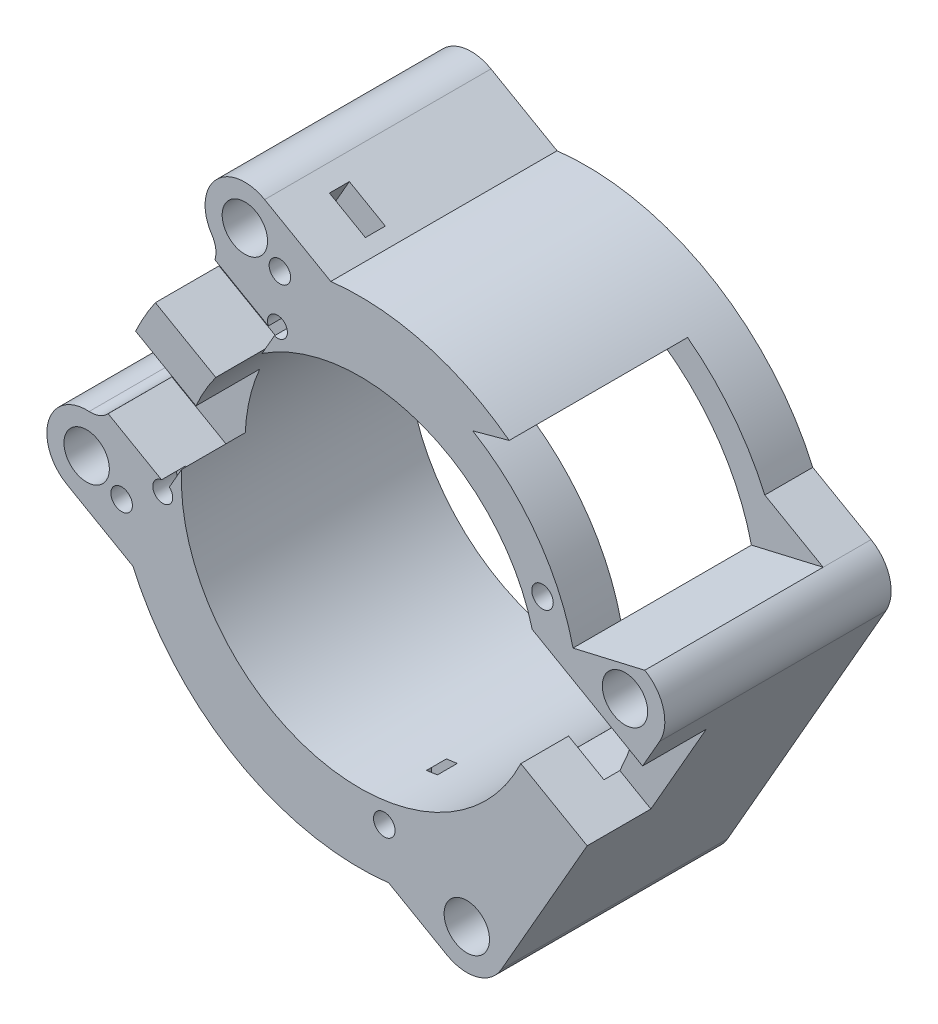
SolidWorks part; units mm, degrees
ref_plane "Front Plane" through (0, 0, 0) normal (0, 0, 1) x (1, 0, 0)
ref_plane "Top Plane" through (0, 0, 0) normal (0, 1, 0) x (1, 0, 0)
ref_plane "Right Plane" through (0, 0, 0) normal (1, 0, 0) x (0, 0, -1)
sketch "Sketch1" plane through (0, 0, 0) normal (0, 0, 1) x (1, 0, 0)
  line L0 (343.92, -196.825) -> (323.9579, -185.4007) construction
  line L1 (323.9579, -185.4007) -> (333.8921, -168.0424) construction
  line L2 (343.92, -196.825) -> (356.9388, -204.2756) construction
  line L3 (356.9388, -204.2756) -> (366.8729, -186.9173) construction
  line L4 (381.5729, -195.33) -> (361.7045, -230.0467) construction
  line L5 (350.2637, -176.9635) -> (357.8812, -174.8913) construction
  line L6 (367.0681, -208.6641) -> (359.4506, -210.7362) construction
  line L7 (350.2637, -176.9635) -> (357.8812, -174.8913) construction
  line L8 (367.0681, -208.6641) -> (359.4506, -210.7362) construction
  line L9 (350.381, -175.377) -> (358.1166, -173.2728)
  line L10 (368.091, -209.9404) -> (360.3554, -212.0446)
  line L11 (368.091, -209.9404) -> (359.8443, -212.1836) construction
  line L12 (349.8699, -175.5161) -> (358.1166, -173.2728) construction
  line L13 (315.4468, -209.3344) -> (21.5627, -41.1449) construction
  line L14 (354.8814, -231.9028) -> (347.5578, -227.7115) construction
  line L15 (372.3932, -184.3156) -> (379.7168, -188.5069) construction
  line L16 (32.0065, 10.4873) -> (340.2822, -165.9385) construction
  line L17 (315.4468, -209.3344) -> (307.1459, -204.5838)
  line L18 (354.8814, -231.9028) -> (347.5578, -227.7115)
  line L19 (381.5729, -195.33) -> (361.7045, -230.0467)
  line L20 (372.3932, -184.3156) -> (379.7168, -188.5069)
  line L21 (331.9813, -161.1879) -> (340.2822, -165.9385)
  circle A0 centre (329.4978, -165.5275) radius 1.65 construction
  circle A1 centre (309.6295, -200.2442) radius 1.65 construction
  circle A2 centre (357.3649, -227.5632) radius 1.65 construction
  circle A3 centre (377.2333, -192.8465) radius 1.65 construction
  circle A4 centre (329.4978, -165.5275) radius 1.65
  circle A5 centre (309.6295, -200.2442) radius 1.65
  circle A6 centre (357.3649, -227.5632) radius 1.65
  circle A7 centre (377.2333, -192.8465) radius 1.65
  circle A8 centre (333.8921, -168.0424) radius 1.35
  circle A9 centre (366.8729, -186.9173) radius 1.35
  circle A10 centre (347.0046, -221.634) radius 1.35
  circle A11 centre (314.0237, -202.7591) radius 1.35
  circle A12 centre (343.92, -196.825) radius 20.9 construction
  arc A13 (323.7528, -202.3109) -> (364.0872, -191.3391) centre (343.92, -196.825) ccw construction
  arc A14 (367.0681, -208.6641) -> (357.8812, -174.8913) centre (343.92, -196.825) ccw construction
  arc A15 (367.0681, -208.6641) -> (357.8812, -174.8913) centre (343.92, -196.825) ccw construction
  arc A16 (368.091, -209.9404) -> (358.1166, -173.2728) centre (343.92, -196.825) ccw
  arc A17 (350.381, -175.377) -> (360.3554, -212.0446) centre (343.92, -196.825) ccw
  circle A18 centre (343.92, -196.825) radius 22.4 construction
  arc A19 (315.4468, -209.3344) -> (347.5578, -227.7115) centre (343.92, -196.825) ccw construction
  arc A20 (354.8814, -231.9028) -> (361.7045, -230.0467) centre (357.3649, -227.5632) ccw construction
  arc A21 (381.5729, -195.33) -> (379.7168, -188.5069) centre (377.2333, -192.8465) ccw construction
  arc A22 (372.3932, -184.3156) -> (340.2822, -165.9385) centre (343.92, -196.825) ccw construction
  arc A23 (315.4468, -209.3344) -> (347.5578, -227.7115) centre (343.92, -196.825) ccw
  arc A24 (354.8814, -231.9028) -> (361.7045, -230.0467) centre (357.3649, -227.5632) ccw
  arc A25 (381.5729, -195.33) -> (379.7168, -188.5069) centre (377.2333, -192.8465) ccw
  arc A26 (372.3932, -184.3156) -> (340.2822, -165.9385) centre (343.92, -196.825) ccw
  arc A27 (307.1459, -204.5838) -> (309.9404, -195.2539) centre (309.6295, -200.2442) cw
  arc A28 (313.1, -192.6614) -> (324.7178, -172.361) centre (343.92, -196.825) cw
  arc A29 (309.9404, -195.2539) -> (313.1, -192.6614) centre (310.127, -192.2597) ccw
  arc A30 (324.7178, -172.361) -> (325.3526, -168.3235) centre (322.8655, -170.0011) ccw
  arc A31 (325.3526, -168.3235) -> (331.9813, -161.1879) centre (329.4978, -165.5275) cw
  point P12 (343.92, -196.825)
  dimension "D1" = 23
  dimension "D4" = 2.7
  dimension "D5" = 1.5
  dimension "D7" = 3
  dimension "D2" = 15
  dimension "D3" = 20
  dimension "D6" = 1.5
extrude "Boss-Extrude1" add sketch "Sketch1" along normal offset from surface (28.42 mm away) 6 contours L20 A26 L21 L17 A23 L18 A24 L19 A25 A11 A4 A5 A6 A7 A8 A10 A17 L9 A16 L10 | A10 | A11 | A8 region at (311.8223, -206.0401, 0) region at (333.8921, -168.0424, 0) region at (347.0046, -221.634, 0) region at (314.0237, -202.7591, 0) offset beyond the face yes
sketch "Sketch3" plane through (0, 0, 28.42) normal (0, 0, 1) x (1, 0, 0)
  line L0 (350.381, -175.377) -> (358.1166, -173.2728) construction
  line L1 (368.091, -209.9404) -> (360.3554, -212.0446) construction
  line L2 (350.381, -175.377) -> (358.1166, -173.2728)
  line L3 (368.091, -209.9404) -> (360.3554, -212.0446)
  arc A0 (368.091, -209.9404) -> (358.1166, -173.2728) centre (343.92, -196.825) ccw construction
  arc A1 (350.381, -175.377) -> (360.3554, -212.0446) centre (343.92, -196.825) ccw construction
  arc A2 (368.091, -209.9404) -> (358.1166, -173.2728) centre (343.92, -196.825) ccw
  arc A3 (350.381, -175.377) -> (360.3554, -212.0446) centre (343.92, -196.825) ccw construction
  arc A4 (350.381, -175.377) -> (360.3554, -212.0446) centre (343.92, -196.825) cw
extrude "Boss-Extrude2" add sketch "Sketch3" against normal blind 6
sketch "Sketch4" plane through (0, 0, 6.02) normal (0, 0, 1) x (1, 0, 0)
  line L1 (350.381, -175.377) -> (358.1166, -173.2728) construction
  line L3 (350.381, -175.377) -> (358.1166, -173.2728) construction
  line L4 (358.1166, -173.2728) -> (362.6908, -172.0285)
  line L5 (379.7168, -188.5069) -> (370.7063, -190.6007)
  line L6 (372.3932, -184.3156) -> (379.7168, -188.5069)
  arc A0 (372.3932, -184.3156) -> (340.2822, -165.9385) centre (343.92, -196.825) ccw construction
  arc A1 (368.091, -209.9404) -> (358.1166, -173.2728) centre (343.92, -196.825) ccw construction
  arc A2 (372.3932, -184.3156) -> (362.6908, -172.0285) centre (343.92, -196.825) ccw
  arc A3 (370.7063, -190.6007) -> (358.1166, -173.2728) centre (343.92, -196.825) ccw
extrude "Cut-Extrude1" cut sketch "Sketch4" along normal through all
sketch "Sketch2" plane through (0, 0, 28.42) normal (0, 0, 1) x (1, 0, 0)
  circle A0 centre (333.8921, -168.0424) radius 1.35 construction
  circle A1 centre (366.8729, -186.9173) radius 1.35 construction
  circle A2 centre (347.0046, -221.634) radius 1.35 construction
  circle A3 centre (314.0237, -202.7591) radius 1.35 construction
  circle A4 centre (333.8921, -168.0424) radius 1.35
  circle A5 centre (366.8729, -186.9173) radius 1.35
  circle A6 centre (347.0046, -221.634) radius 1.35
  circle A7 centre (314.0237, -202.7591) radius 1.35
extrude "Cut-Extrude2" cut sketch "Sketch2" against normal blind 10
sketch "Sketch5" plane through (0, 0, 28.42) normal (0, 0, 1) x (1, 0, 0)
  line L0 (315.4468, -209.3344) -> (307.1459, -204.5838) construction
  line L1 (347.3223, -218.6486) -> (344.5781, -219.8662)
  line L2 (344.5781, -219.8662) -> (344.2603, -222.8515)
  line L3 (344.2603, -222.8515) -> (346.6869, -224.6193) construction
  line L4 (346.6869, -224.6193) -> (349.4311, -223.4018) construction
  line L5 (349.4311, -223.4018) -> (349.7489, -220.4164)
  line L6 (349.7489, -220.4164) -> (347.3223, -218.6486)
  line L7 (317.0259, -202.7477) -> (315.515, -200.1534)
  line L8 (315.515, -200.1534) -> (312.5128, -200.1648)
  line L9 (312.5128, -200.1648) -> (311.0215, -202.7705)
  line L10 (311.0215, -202.7705) -> (312.5325, -205.3647) construction
  line L11 (312.5325, -205.3647) -> (315.5347, -205.3533) construction
  line L12 (315.5347, -205.3533) -> (317.0259, -202.7477)
  line L13 (336.8943, -168.031) -> (335.3833, -165.4367) construction
  line L14 (335.3833, -165.4367) -> (332.3811, -165.4481) construction
  line L15 (332.3811, -165.4481) -> (330.8899, -168.0538)
  line L16 (330.8899, -168.0538) -> (332.4008, -170.648)
  line L17 (332.4008, -170.648) -> (335.403, -170.6366)
  line L18 (335.403, -170.6366) -> (336.8943, -168.031)
  line L19 (331.9813, -161.1879) -> (340.2822, -165.9385) construction
  line L20 (311.0215, -202.7705) -> (309.2836, -205.8072)
  line L21 (309.2836, -205.8072) -> (313.7968, -208.3901)
  line L22 (313.7968, -208.3901) -> (315.5347, -205.3533)
  line L23 (336.8943, -168.031) -> (338.6322, -164.9942)
  line L24 (338.6322, -164.9942) -> (334.119, -162.4113)
  line L25 (334.119, -162.4113) -> (332.3811, -165.4481)
  line L26 (347.0046, -221.634) -> (347.3223, -218.6486) construction
  line L27 (349.4311, -223.4018) -> (348.8913, -228.4746)
  line L28 (354.8814, -231.9028) -> (347.5578, -227.7115) construction
  line L29 (348.8913, -228.4746) -> (343.7205, -227.9244)
  line L30 (343.7205, -227.9244) -> (344.2603, -222.8515)
  circle A0 centre (347.0046, -221.634) radius 2.6 construction
  circle A1 centre (314.0237, -202.7591) radius 2.6 construction
  circle A2 centre (333.8921, -168.0424) radius 2.6 construction
  arc A3 (315.4468, -209.3344) -> (347.5578, -227.7115) centre (343.92, -196.825) ccw construction
  dimension "D1" = 5.2
extrude "Cut-Extrude3" cut sketch "Sketch5" against normal blind 2.5 from offset 6 offset against normal yes
sketch "Sketch6" plane through (0, 0, 28.42) normal (0, 0, 1) x (1, 0, 0)
  circle A2 centre (309.6295, -200.2442) radius 2.85
  circle A3 centre (329.4978, -165.5275) radius 2.85
  circle A4 centre (357.3649, -227.5632) radius 2.85
  circle A5 centre (377.2333, -192.8465) radius 2.85
  dimension "D1" = 5.7
extrude "Cut-Extrude4" cut sketch "Sketch6" against normal offset from surface (25.42 mm away) 3
sketch "Sketch7" plane through (0, 0, 28.42) normal (0, 0, 1) x (1, 0, 0)
  line L0 (307.0857, -190.7231) -> (319.7139, -197.9502) construction
  line L1 (307.0857, -190.7231) -> (312.0528, -182.044) construction
  line L2 (319.7139, -197.9502) -> (324.681, -189.2711) construction
  line L3 (312.0528, -182.044) -> (324.681, -189.2711) construction
  line L4 (321.5765, -194.6956) -> (320.3348, -196.8653) construction
  line L5 (315.033, -176.8365) -> (327.6612, -184.0636) construction
  line L6 (315.033, -176.8365) -> (320.0001, -168.1573) construction
  line L7 (327.6612, -184.0636) -> (332.6283, -175.3844) construction
  line L8 (320.0001, -168.1573) -> (332.6283, -175.3844) construction
  line L9 (314.3507, -177.0221) -> (327.8468, -184.7459)
  line L10 (327.8468, -184.7459) -> (333.3106, -175.1988)
  line L17 (319.8145, -167.475) -> (333.3106, -175.1988)
  line L18 (314.3507, -177.0221) -> (319.8145, -167.475)
  line L19 (311.8672, -181.3617) -> (325.3633, -189.0855)
  line L20 (319.8995, -198.6326) -> (325.3633, -189.0855)
  line L21 (306.4034, -190.9087) -> (319.8995, -198.6326)
  line L22 (306.4034, -190.9087) -> (311.8672, -181.3617)
  line L23 (356.544, -200.9388) -> (360.8836, -203.4224) construction
  line L24 (356.544, -200.9388) -> (362.5045, -190.5238) construction
  line L25 (360.8836, -203.4224) -> (366.8441, -193.0074) construction
  line L26 (362.5045, -190.5238) -> (366.8441, -193.0074) construction
  line L27 (361.2548, -204.787) -> (368.2088, -192.6361) construction
  line L28 (362.1333, -189.1592) -> (368.2088, -192.6361)
  line L29 (355.1794, -201.31) -> (362.1333, -189.1592)
  line L30 (355.1794, -201.31) -> (361.2548, -204.787)
  line L31 (368.2088, -192.6361) -> (379.437, -199.0621)
  line L32 (381.5729, -195.33) -> (361.7045, -230.0467) construction
  line L33 (379.437, -199.0621) -> (372.4831, -211.2129)
  line L34 (372.4831, -211.2129) -> (361.2548, -204.787)
  dimension "D1" = 0.5
  dimension "D2" = 1
  dimension "D3" = 90
extrude "Cut-Extrude5" cut sketch "Sketch7" against normal blind 8
sketch "Sketch9" plane through (0, 0, 28.42) normal (0, 0, 1) x (1, 0, 0)
  circle A0 centre (333.5903, -174.2067) radius 0.75 construction
  circle A1 centre (331.5026, -180.2706) radius 0.4 construction
  circle A2 centre (328.87, -184.8706) radius 0.4 construction
  circle A3 centre (326.3881, -186.7915) radius 0.75 construction
  circle A4 centre (322.6612, -195.7196) radius 0.4 construction
  circle A5 centre (319.1858, -199.3763) radius 0.75 construction
  circle A6 centre (333.5903, -174.2067) radius 0.75 construction
  circle A7 centre (331.5026, -180.2706) radius 0.4 construction
  circle A8 centre (328.87, -184.8706) radius 0.4 construction
  circle A9 centre (326.3881, -186.7915) radius 0.75 construction
  circle A10 centre (322.6612, -195.7196) radius 0.4 construction
  circle A11 centre (319.1858, -199.3763) radius 0.75 construction
  circle A12 centre (333.5903, -174.2067) radius 1.25
  circle A13 centre (331.5026, -180.2706) radius 0.9
  circle A14 centre (328.87, -184.8706) radius 0.9
  circle A15 centre (326.3881, -186.7915) radius 1.25
  circle A16 centre (322.6612, -195.7196) radius 0.9
  circle A17 centre (319.1858, -199.3763) radius 1.25
  dimension "D1" = 0.5
extrude "Cut-Extrude6" cut sketch "Sketch9" against normal blind 3
equation "\"D1@Boss-Extrude1\"=3.3+2+0.7"
